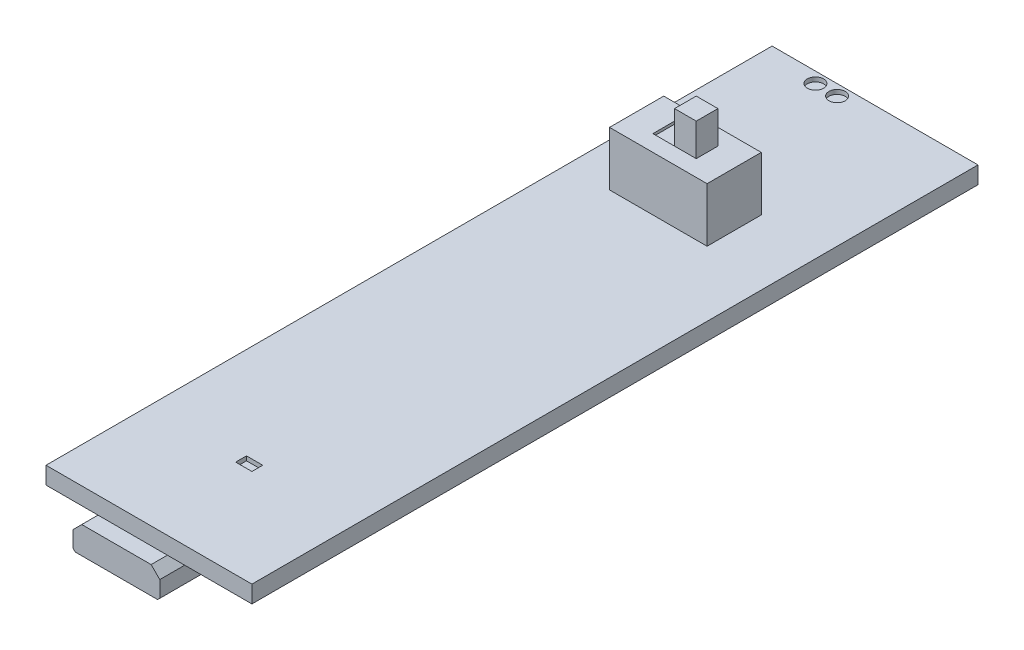
SolidWorks part; units mm, degrees
material "Aluminum Bronze"
ref_plane "Front" through (0, 0, 0) normal (0, 0, 1) x (1, 0, 0)
ref_plane "Top" through (0, 0, 0) normal (0, 1, 0) x (1, 0, 0)
ref_plane "Right" through (0, 0, 0) normal (1, 0, 0) x (0, 0, -1)
sketch "Sketch1" plane through (0, 0, 0) normal (0, 1, 0) x (1, 0, 0)
  line L1 (-9.5, 33.5) -> (9.5, 33.5)
  line L2 (-9.5, 33.5) -> (-9.5, -33.5)
  line L3 (-9.5, -33.5) -> (9.5, -33.5)
  line L4 (9.5, 33.5) -> (9.5, -33.5)
  line L5 (-9.5, 33.5) -> (9.5, -33.5) construction
  line L6 (-9.5, -33.5) -> (9.5, 33.5) construction
  point P0 (0, 0)
  dimension "D1" = 19
  dimension "D2" = 67
extrude "Boss-Extrude1" add sketch "Sketch1" along normal mid plane 1.5875
sketch "Sketch3" plane through (0, 0.7937, 0) normal (0, 1, 0) x (1, 0, 0)
  line L0 (9.5, 33.5) -> (-9.5, 33.5) construction
  line L1 (-5.5, 19.5) -> (3.5, 19.5)
  line L2 (-5.5, 19.5) -> (-5.5, 14.5)
  line L3 (-5.5, 14.5) -> (3.5, 14.5)
  line L4 (3.5, 19.5) -> (3.5, 14.5)
  line L5 (9.5, -33.5) -> (9.5, 33.5) construction
  dimension "D1" = 19
  dimension "D2" = 15
  dimension "D3" = 9
  dimension "D4" = 5
extrude "Boss-Extrude2" add sketch "Sketch3" along normal blind 5
sketch "Sketch4" plane through (0, 5.7938, 0) normal (0, 1, 0) x (1, 0, 0)
  line L0 (3.5, 14.5) -> (3.5, 19.5) construction
  line L1 (-1, 18) -> (1, 18)
  line L2 (-1, 18) -> (-1, 16)
  line L3 (-1, 16) -> (1, 16)
  line L4 (1, 18) -> (1, 16)
  line L5 (-1, 18) -> (1, 16) construction
  line L6 (-1, 16) -> (1, 18) construction
  line L7 (3.5, 14.5) -> (3.5, 19.5) construction
  line L8 (-5.5, 19.5) -> (-5.5, 14.5) construction
  line L9 (1, 18) -> (-3, 18)
  line L10 (1, 18) -> (1, 16)
  line L11 (1, 16) -> (-3, 16)
  line L12 (-3, 18) -> (-3, 16)
  point P0 (0, 17)
  point P5 (3.5, 17)
  point P13 (-3.4644, 16)
  dimension "D1" = 2
  dimension "D2" = 2.5
  dimension "D3" = 2.5
extrude "Cut-Extrude2" cut sketch "Sketch4" against normal blind 0.25 contours L9 L12 L11 L2 | L4 L1 L2 L3 region at (0, 5.7938, -17) region at (-2, 5.7938, -17)
extrude "Boss-Extrude3" add sketch "Sketch4<3>" along normal blind 3 and the other way up to surface (0.25 mm away) contours L4 L1 L2 L3 region at (0, 5.7938, -17) other way up to face at (-1, 5.5438, -17)
sketch "Sketch4<3>" plane through (0, 5.7938, 0) normal (0, 1, 0) x (1, 0, 0) same geometry as "Sketch4"
ref_plane "Plane1" through (0, 0, 35) normal (0, 0, 1) x (1, 0, 0)
sketch "Sketch5" plane through (0, 0, 35) normal (0, 0, 1) x (1, 0, 0)
  line L0 (-9.5, -0.7937) -> (9.5, -0.7937) construction
  line L1 (-5.5, -0.7937) -> (2.5, -0.7937)
  line L2 (-5.5, -0.7937) -> (-5.5, -3.2937)
  line L3 (-5.5, -3.2937) -> (2.5, -3.2937)
  line L4 (2.5, -0.7937) -> (2.5, -3.2937)
  line L5 (-9.5, 0.7937) -> (-9.5, -0.7937) construction
  point P7 (0, 0)
  point P10 (0, 0)
  dimension "D1" = 8
  dimension "D2" = 12
  dimension "D3" = 2.5
extrude "Boss-Extrude4" add sketch "Sketch5" against normal blind 6 separate body
sketch "Sketch2" plane through (0, 0.7937, 0) normal (0, 1, 0) x (1, 0, 0)
  line L0 (-9.5, 33.5) -> (-9.5, -33.5) construction
  line L1 (9.5, 33.5) -> (-9.5, 33.5) construction
  line L2 (-9.5, -33.5) -> (9.5, -33.5) construction
  line L3 (-1, -23.5) -> (0.5, -23.5)
  line L4 (-1, -23.5) -> (-1, -24.5)
  line L5 (-1, -24.5) -> (0.5, -24.5)
  line L6 (0.5, -23.5) -> (0.5, -24.5)
  circle A0 centre (-4.5, 32.5) radius 0.75
  circle A1 centre (-2.5, 32.5) radius 0.75
  dimension "D1" = 5
  dimension "D4" = 1.5
  dimension "D2" = 7
  dimension "D3" = 1
  dimension "D5" = 10
  dimension "D6" = 10
  dimension "D7" = 1.5
  dimension "D8" = 1
extrude "Cut-Extrude1" cut sketch "Sketch2" against normal blind 0.3969
chamfer "Chamfer1" distance 0.8 angle 45 2 edges at (2.5, -0.7937, 32) (-5.5, -0.7937, 32)
chamfer "Chamfer2" distance 0.2 angle 45 2 edges at (2.5, -3.2937, 32) (-5.5, -3.2937, 32)
